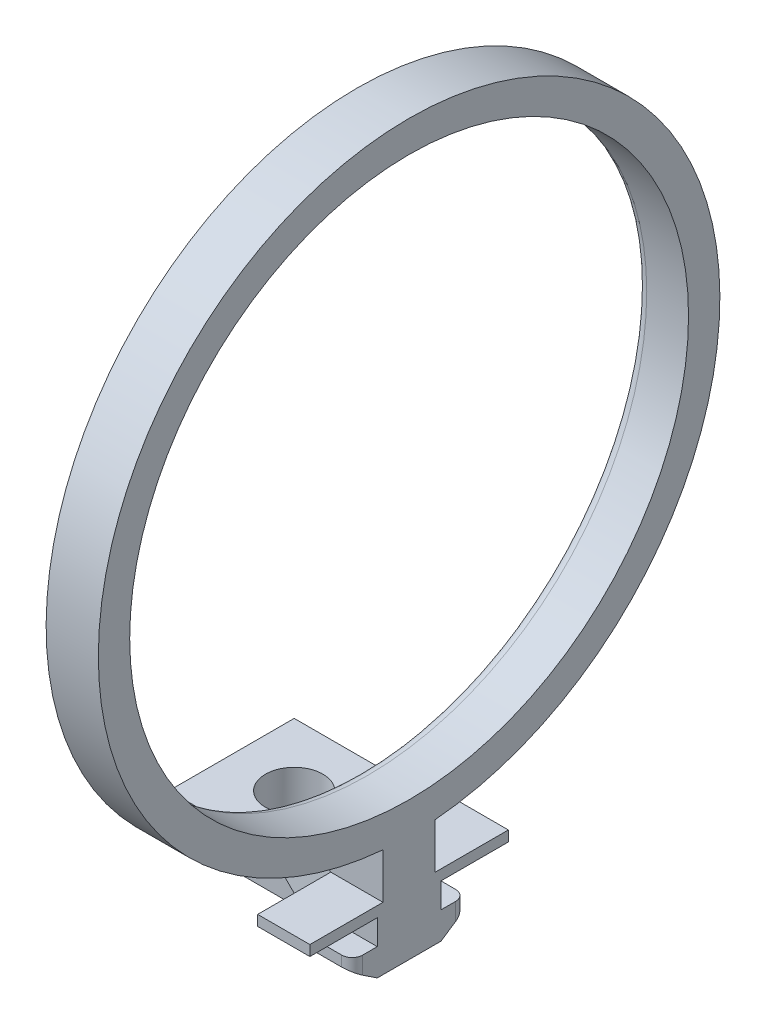
SolidWorks part; units mm, degrees
ref_plane "Front Plane" through (0, 0, 0) normal (0, 0, 1) x (1, 0, 0)
ref_plane "Top Plane" through (0, 0, 0) normal (0, 1, 0) x (1, 0, 0)
ref_plane "Right Plane" through (0, 0, 0) normal (1, 0, 0) x (0, 0, -1)
sketch "Sketch1" plane through (0, 0, 0) normal (1, 0, 0) x (0, 0, -1)
  line L0 (26.75, 0) -> (29.75, 0)
  line L1 (26.75, 0) -> (26.5, 0)
  circle A0 centre (0, 0) radius 26.5 construction
  circle A1 centre (0, 0) radius 26.75
  circle A2 centre (0, 0) radius 29.75
  circle A3 centre (0, 0) radius 26.5 construction
  dimension "D1" = 3
  dimension "D2" = 0.25
extrude "Boss-Extrude1" add sketch "Sketch1" against normal blind 5 contours A2 A1 region at (0, 0, 28.9085)
sketch "Sketch2" plane through (0, 0, 0) normal (1, 0, 0) x (0, 0, -1)
  line L0 (0, -29.75) -> (0, -35) construction
  line L5 (-2.5, -35) -> (2.5, -35)
  line L6 (2.5, -35) -> (2.5, -29.6448)
  line L7 (-2.5, -35) -> (-2.5, -29.6448)
  line L8 (2.5, -32.3224) -> (-2.5, -32.3224) construction
  line L9 (-2.5, -29.6448) -> (2.5, -29.6448)
  circle A0 centre (0, 0) radius 29.75 construction
  circle A1 centre (0, 0) radius 29.75 construction
  point P10 (0, -35)
  dimension "D1" = 5
extrude "Boss-Extrude2" add sketch "Sketch2" against normal blind 5
sketch "Sketch3" plane through (0, 0, 0) normal (1, 0, 0) x (0, 0, -1)
  line L1 (-2.5, -35) -> (2.5, -35) construction
  line B0 (0, -40) -> (0, -35) construction
  line B1 (-9.5, -35) -> (-9.5, -34)
  line B2 (-3.05, -35) -> (3.05, -35) construction
  line B3 (-3.05, -35) -> (-3.05, -37.4)
  line B4 (3.05, -35) -> (3.05, -37.4)
  line B5 (-3.05, -37.4) -> (-5.45, -37.4)
  line B6 (-5.45, -37.4) -> (-5.45, -38.4)
  line B7 (3.05, -37.4) -> (5.45, -37.4)
  line B8 (5.45, -37.4) -> (5.45, -38.4)
  line B9 (-3.05, -35) -> (-9.5, -35)
  line B10 (-9.5, -34) -> (9.5, -34)
  line B11 (3.05, -35) -> (9.5, -35)
  line B12 (9.5, -34) -> (9.5, -35)
  line B13 (-3.05, -37.4) -> (-3.05, -40) construction
  line B14 (-5.45, -38.4) -> (-3.05, -40)
  line B15 (3.05, -37.4) -> (3.05, -40) construction
  line B16 (5.45, -38.4) -> (3.05, -40)
  line B17 (3.05, -40) -> (-3.05, -40)
sketch_block_instance "Block-2020 rail insert-1"
sketch_block "Block-2020 rail insert" parameters "D1"=5, "D2"=6.1, "D3"=2.4, "D4"=2.4, "D5"=1, "D6"=1, "D7"=19
extrude "Boss-Extrude3" add sketch "Sketch3" against normal blind 5
fillet "Fillet1" radius 1 2 edges at (0, -37.9, 5.45) (0, -37.9, -5.45)
sketch "Sketch38" plane through (-5, 0, 0) normal (-1, 0, 0) x (0, 0, 1)
  line L0 (2.5, -33.25) -> (-2.5, -33.25) construction
  line L1 (2.5, -29.6448) -> (2.5, -34) construction
  line L2 (-2.5, -34) -> (-2.5, -29.6448) construction
  line L3 (-6, -31.5) -> (6, -31.5)
  line L4 (-6, -31.5) -> (-6, -35)
  line L5 (-6, -35) -> (6, -35)
  line L6 (6, -31.5) -> (6, -35)
  line L7 (-6, -31.5) -> (6, -35) construction
  line L8 (-6, -35) -> (6, -31.5) construction
  dimension "D1" = 12
  dimension "D2" = 3.5
extrude "Boss-Extrude28" add sketch "Sketch38" along normal blind 12
sketch "Sketch39" plane through (0, -31.5, 0) normal (0, 1, 0) x (1, 0, 0)
  line L0 (-17, -6) -> (-5, 6) construction
  circle A0 centre (-11, 0) radius 2.75
  dimension "D1" = 5.5
extrude "Cut-Extrude3" cut sketch "Sketch39" against normal up to next contours A0
chamfer "Chamfer1" distance 2.5 angle 45 2 edges at (-5, -31.5, 4.25) (-5, -31.5, -4.25)
fillet "Fillet3" radius 1 1 edges at (-5, 0, -26.75)
ref_axis "Axis1" through (0, -35, 0) along (1, 0, 0)
